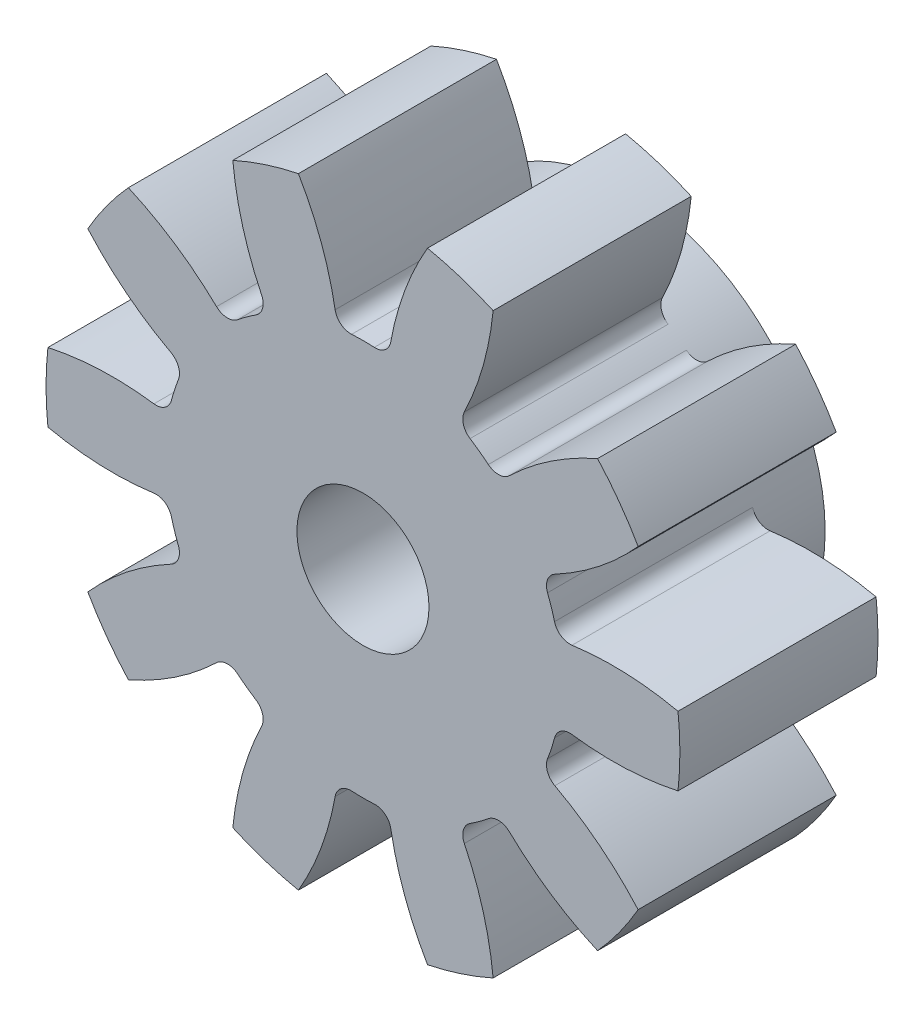
SolidWorks part; units mm, degrees
ref_plane "Front Plane" through (0, 0, 0) normal (0, 0, 1) x (1, 0, 0)
ref_plane "Top Plane" through (0, 0, 0) normal (0, 1, 0) x (1, 0, 0)
ref_plane "Right Plane" through (0, 0, 0) normal (1, 0, 0) x (0, 0, -1)
sketch "Sketch1" plane through (0, 0, 0) normal (0, 0, 1) x (1, 0, 0)
  circle A0 centre (0, 0) radius 10
  circle A1 centre (0, 0) radius 12
  circle A2 centre (0, 0) radius 7.5
  dimension "D1" = 20
  dimension "D2" = 24
  dimension "D3" = 4.5
extrude "Boss-Extrude1" add sketch "Sketch1" along normal mid plane 425 contours A1
sketch "Sketch2" plane through (0, 0, 0) normal (0, 0, 1) x (1, 0, 0)
  line L0 (0, 0) -> (0, 12) construction
  line L1 (-1.5643, 9.8769) -> (1.5643, 9.8769) construction
  line L2 (-0.9691, 7.4371) -> (0, 0) construction
  line L3 (0, 5.5789) -> (-2.6051, 12.7363) construction
  line L4 (0, 0) -> (3.7082, 11.4127) construction
  line L5 (1.5643, 9.8769) -> (4.5399, 8.9101) construction
  circle A0 centre (0, 0) radius 12 construction
  arc A1 (-3.0254, 12.6431) -> (-0.9691, 7.4371) centre (-12.3373, 5.9558) cw
  arc A2 (3.0254, 12.6431) -> (0.9691, 7.4371) centre (12.3373, 5.9558) ccw
  circle A3 centre (0, 0) radius 7.5 construction
  arc A4 (0.9691, 7.4371) -> (-0.9691, 7.4371) centre (0, 0) ccw
  circle A5 centre (0, 0) radius 12 construction
  circle A6 centre (0, 0) radius 10 construction
  circle A7 centre (0, 0) radius 13
  arc A8 (3.0254, 12.6431) -> (-3.0254, 12.6431) centre (0, 0) ccw
  dimension "D2" = 1.9081
  dimension "D3" = 20
  dimension "D4" = 18
extrude "Cut-Extrude1" cut sketch "Sketch2" against normal through all both and the other way through all
fillet "Fillet1" radius 0.6 1 edges at (-0.9691, 7.4371, 0) type face fillet first side face at (-1.5984, 9.6298, 0) second side face at (0, 7.4686, 0)
fillet "Fillet2" radius 0.6 1 edges at (0.9691, 7.4371, 0) type face fillet first side face at (1.5984, 9.6298, 0) second side face at (0.2709, 7.4788, 0)
sketch "Sketch3" plane through (0, 0, -212.5) normal (0, 0, -1) x (-1, 0, 0)
pattern_circular "CirPattern2" count 10 over 360 about axis through (0, 0, 212.5) along (0, 0, 1) of "Cut-Extrude1", "Fillet1", "Fillet2"
sketch "Sketch4" plane through (0, 0, -212.5) normal (0, 0, -1) x (-1, 0, 0)
  circle A0 centre (0, 0) radius 7.5
  circle A1 centre (0, 0) radius 2.5
  dimension "D1" = 5
extrude "Boss-Extrude2" add sketch "Sketch4" along normal mid plane 5 contours A0 | A1
sketch "Sketch5" plane through (0, 0, -212.5) normal (0, 0, -1) x (-1, 0, 0)
  circle A0 centre (0, 0) radius 3
extrude "Cut-Extrude2" cut sketch "Sketch5" against normal blind 32 and the other way through all
sketch "Sketch6" plane through (0, 0, 212.5) normal (0, 0, 1) x (1, 0, 0)
  circle A0 centre (0, 0) radius 7.5
  dimension "D1" = 15
extrude "Boss-Extrude3" add sketch "Sketch6" along normal mid plane 12
ref_plane "Plane1" through (0, 0, -205) normal (0, 0, -1) x (-1, 0, 0)
sketch "Sketch7" plane through (0, 0, 218.5) normal (0, 0, 1) x (1, 0, 0)
  circle A0 centre (0, 0) radius 12
extrude "Cut-Extrude3" cut sketch "Sketch7" against normal up to surface (423.5 mm away) contours A0 up to plane "Plane1"
sketch "Sketch8" plane through (0, 0, -215) normal (0, 0, -1) x (-1, 0, 0)
  circle A0 centre (0, 0) radius 1.65
  circle A1 centre (0, 0) radius 7.5
  dimension "D1" = 3.3
extrude "Boss-Extrude4" add sketch "Sketch8" against normal up to surface (10 mm away) up to face at (-3, 0, -205)
sketch "Sketch9" plane through (0, 0, -185.7941) normal (0, 0, 1) x (1, 0, 0)
  circle A0 centre (0, 0) radius 2.5
  dimension "D1" = 5
extrude "Cut-Extrude4" cut sketch "Sketch9" against normal through all contours A0
equation "\"Module\"= 2mm"
equation "\"Number of Teeth\"= 10"
equation "\"D1@Sketch1\"=\"Module\" * \"Number of Teeth\""
equation "\"D2@Sketch1\"=(\"Number of Teeth\" + 2) * \"Module\""
equation "\"D3@Sketch1\"=\"Module\" * if( \"Module\" = > 1.25, 2.25, 2.4)"
equation "\"D4@Sketch2\"=180 / \"Number of Teeth\""
equation "\"D1@Fillet1\"=0.3 * \"Module\""
